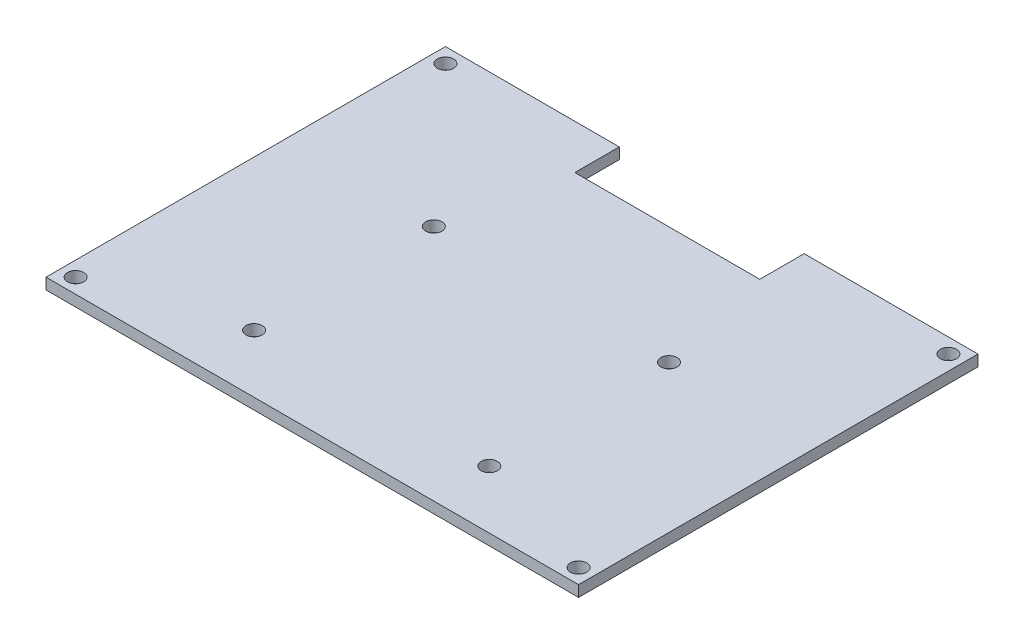
SolidWorks part; units mm, degrees
ref_plane "Front Plane" through (0, 0, 0) normal (0, 0, 1) x (1, 0, 0)
ref_plane "Top Plane" through (0, 0, 0) normal (0, 1, 0) x (1, 0, 0)
ref_plane "Right Plane" through (0, 0, 0) normal (1, 0, 0) x (0, 0, -1)
sketch "Sketch1" plane through (0, 0, 0) normal (0, 1, 0) x (1, 0, 0)
  line L1 (0, 0) -> (72, 0)
  line L2 (0, 0) -> (0, 54)
  line L3 (0, 54) -> (72, 54)
  line L4 (72, 0) -> (72, 54)
  dimension "D1" = 72
  dimension "D2" = 54
extrude "Boss-Extrude1" add sketch "Sketch1" along normal blind 1.5
sketch "Sketch2" plane through (0, 1.5, 0) normal (0, 1, 0) x (1, 0, 0)
  line L0 (72, 54) -> (0, 54) construction
  line L1 (23.5, 54) -> (48.5, 54)
  line L2 (23.5, 54) -> (23.5, 48)
  line L3 (23.5, 48) -> (48.5, 48)
  line L4 (48.5, 54) -> (48.5, 48)
  point P6 (36, 54)
  dimension "D1" = 25
  dimension "D2" = 6
extrude "Cut-Extrude1" cut sketch "Sketch2" against normal up to surface (1.5 mm away) up to face at (36, 0, -27)
sketch "Sketch5" plane through (0, 1.5, 0) normal (0, 1, 0) x (1, 0, 0)
  line L0 (2, 52) -> (2, 54) construction
  line L1 (23.5, 54) -> (0, 54) construction
  line L2 (2, 54) -> (2, 52) construction
  line L3 (2, 52) -> (0, 52) construction
  line L4 (0, 54) -> (0, 0) construction
  line L5 (70, 52) -> (70, 54) construction
  line L6 (72, 54) -> (48.5, 54) construction
  line L7 (70, 52) -> (72, 52) construction
  line L8 (72, 0) -> (72, 54) construction
  circle A0 centre (2, 52) radius 1.1
  circle A1 centre (70, 52) radius 1.1
  dimension "D1" = 2.2
  dimension "D3" = 2
extrude "Cut-Extrude2" cut sketch "Sketch5" against normal up to surface (1.5 mm away) up to face at (36, 0, -39)
ref_plane "Plane1" through (0, 0, -27) normal (0, 0, 1) x (1, 0, 0)
mirror "Mirror1" about plane through (0, 0, -27) normal (0, 0, 1) of "Cut-Extrude2"
sketch "Sketch6" plane through (0, 1.5, 0) normal (0, 1, 0) x (1, 0, 0)
  line L0 (20.28, 7.85) -> (52.08, 7.85) construction
  line L1 (0, 0) -> (72, 0) construction
  line L3 (20.28, 7.85) -> (20.28, 32.15) construction
  line L4 (20.28, 32.15) -> (52.08, 32.15) construction
  line L5 (0, 54) -> (0, 0) construction
  circle A0 centre (20.28, 7.85) radius 1.1
  circle A1 centre (52.08, 7.85) radius 1.1
  circle A2 centre (20.28, 32.15) radius 1.1
  circle A3 centre (52.08, 32.15) radius 1.1
  dimension "D1" = 2.2
  dimension "D2" = 7.85
  dimension "D3" = 31.8
  dimension "D4" = 24.3
  dimension "D5" = 20.28
extrude "Cut-Extrude3" cut sketch "Sketch6" against normal up to surface (1.5 mm away) up to face at (2, 0, -3.1)
